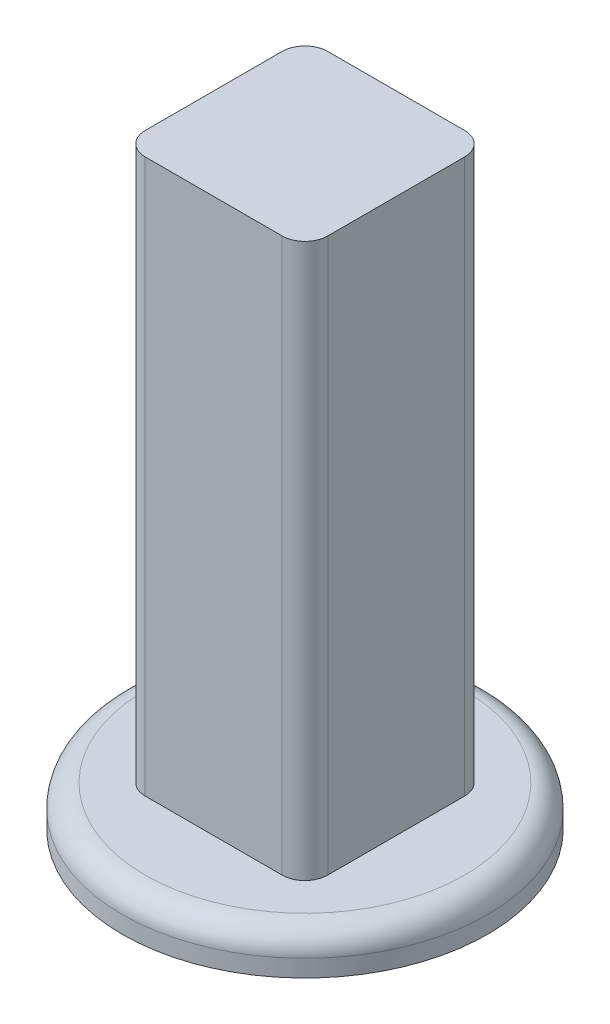
SolidWorks part; units mm, degrees
ref_plane "Front Plane" through (0, 0, 0) normal (0, 0, 1) x (1, 0, 0)
ref_plane "Top Plane" through (0, 0, 0) normal (0, 1, 0) x (1, 0, 0)
ref_plane "Right Plane" through (0, 0, 0) normal (1, 0, 0) x (0, 0, -1)
sketch "Sketch1" plane through (0, 0, 0) normal (0, 1, 0) x (1, 0, 0)
  line L1 (-4, -4) -> (4, -4)
  line L2 (-4, -4) -> (-4, 4)
  line L3 (-4, 4) -> (4, 4)
  line L4 (4, -4) -> (4, 4)
  line L5 (-4, -4) -> (4, 4) construction
  line L6 (-4, 4) -> (4, -4) construction
  circle A0 centre (0, 0) radius 8
  dimension "D1" = 16
  dimension "D2" = 8
  dimension "D3" = 8
extrude "Boss-Extrude1" add sketch "Sketch1" along normal blind 1.75
extrude "Boss-Extrude2" add sketch "Sketch1<2>" along normal blind 26 contours L2 L3 L4 L1
sketch "Sketch1<2>" plane through (0, 0, 0) normal (0, 1, 0) x (1, 0, 0) same geometry as "Sketch1"
fillet "Fillet1" radius 1 5 edges at (-4, 13.875, 4) (4, 13.875, 4) (4, 13.875, -4) (-4, 13.875, -4) (0, 1.75, 8)
